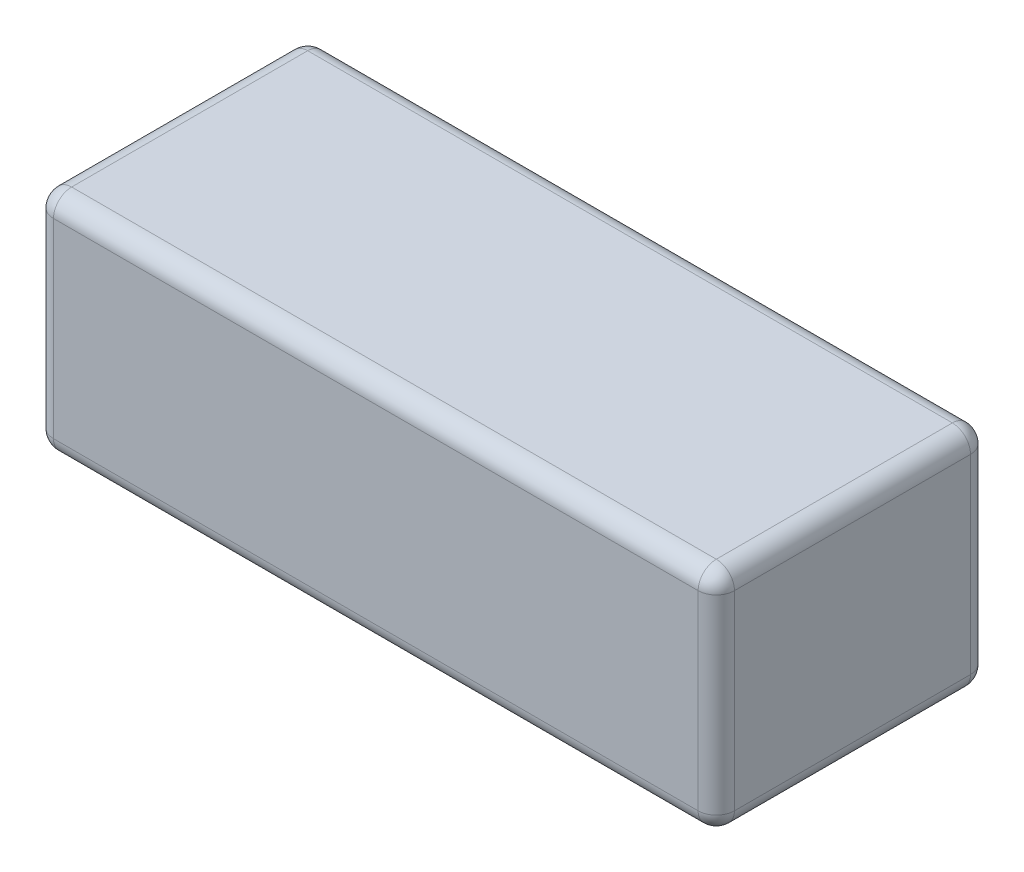
SolidWorks part; units mm, degrees
ref_plane "Front" through (0, 0, 0) normal (0, 0, 1) x (1, 0, 0)
ref_plane "Top" through (0, 0, 0) normal (0, 1, 0) x (1, 0, 0)
ref_plane "Right" through (0, 0, 0) normal (1, 0, 0) x (0, 0, -1)
sketch "Sketch1" plane through (0, 0, 0) normal (0, 1, 0) x (1, 0, 0)
  line L1 (-37.5, 14.9884) -> (37.5, 14.9884)
  line L2 (-37.5, 14.9884) -> (-37.5, -15.0116)
  line L3 (-37.5, -15.0116) -> (37.5, -15.0116)
  line L4 (37.5, 14.9884) -> (37.5, -15.0116)
  dimension "D1" = 75
  dimension "D2" = 30
  dimension "D3" = 37.5
  dimension "D4" = 14.9884
extrude "Boss-Extrude1" add sketch "Sketch1" along normal blind 25 contours L1 L4 L3 L2
fillet "Fillet2" radius 2 12 edges at (0, 25, -14.9884) (-37.5, 12.5, -14.9884) (-37.5, 25, 0.0116) (0, 0, -14.9884) (-37.5, 0, 0.0116) (-37.5, 12.5, 15.0116) (0, 25, 15.0116) (0, 0, 15.0116) (37.5, 12.5, 15.0116) (37.5, 25, 0.0116) (37.5, 12.5, -14.9884) (37.5, 0, 0.0116)
sketch "Sketch2" plane through (0, 0, 0) normal (0, -1, 0) x (1, 0, 0)
  line L0 (-35.5, 13.0116) -> (-35.5, -12.9884) construction
  line L1 (-24.8492, 0) -> (-17.4246, 7.4246)
  line L2 (-24.8492, 0) -> (-17.4246, -7.4246)
  line L3 (-17.4246, -7.4246) -> (-10, 0)
  line L4 (-17.4246, 7.4246) -> (-10, 0)
  line L5 (-35.5, -12.9884) -> (35.5, -12.9884) construction
  text T0 "STM32F103\r\nC8T6" font "Century Gothic" height 6.35
  dimension "D1" = 10.6508
  dimension "D2" = 18.0754
  dimension "D3" = 5.5638
  dimension "D5" = 14.9884
extrude "Cut-Extrude1" cut sketch "Sketch2" against normal blind 1
ref_point "Point1"
ref_point "Point2"
ref_axis "Axis1" through (37.5, 12.5, 0.0116) along (-1, 0, 0)
